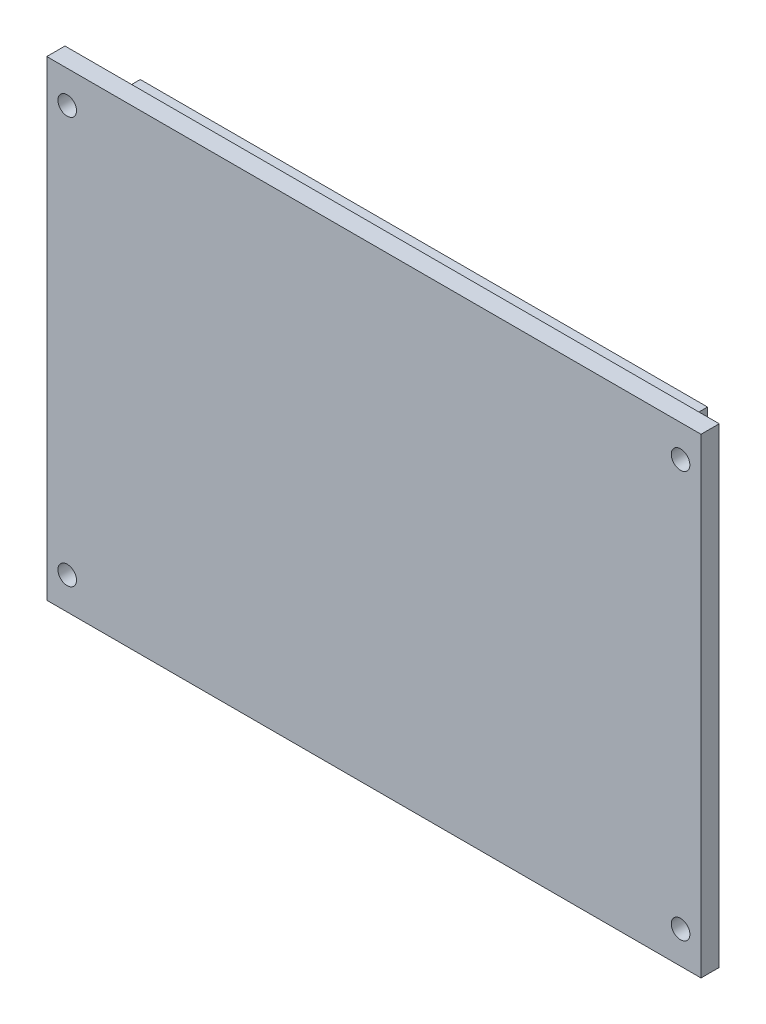
SolidWorks part; units mm, degrees
material "ABS"
ref_plane "Front Plane" through (0, 0, 0) normal (0, 0, 1) x (1, 0, 0)
ref_plane "Top Plane" through (0, 0, 0) normal (0, 1, 0) x (1, 0, 0)
ref_plane "Right Plane" through (0, 0, 0) normal (1, 0, 0) x (0, 0, -1)
sketch "Sketch1" plane through (0, 0, 0) normal (0, 1, 0) x (1, 0, 0)
  circle A0 centre (0, 0) radius 172.5
  dimension "D1" = 345
extrude "Boss-Extrude1" add sketch "Sketch1" along normal blind 10
sketch "Sketch2" plane through (0, 10, 0) normal (0, 1, 0) x (1, 0, 0)
  circle A0 centre (-75.91, -178.72) radius 48.41
  circle A1 centre (75.91, -178.72) radius 48.41
  dimension "D1" = 96.82
  dimension "D2" = 96.82
  dimension "D3" = 151.82
  dimension "D4" = 0
  dimension "D5" = 178.72
  dimension "D6" = 75.91
extrude "Cut-Extrude1" cut sketch "Sketch2" against normal blind 10
sketch "Sketch3" plane through (0, 10, 0) normal (0, 1, 0) x (1, 0, 0)
  line L0 (-75.91, -178.72) -> (75.91, -178.72)
  line L1 (-98.9683, -119.81) -> (98.9683, -119.81)
  line L2 (0, -178.72) -> (0, -205.4095)
  line L3 (0, -116.81) -> (0, -103.1109)
  line L4 (-97.8835, -116.81) -> (97.8835, -116.81)
  arc A0 (97.8835, -116.81) -> (-97.8835, -116.81) centre (0, 0) ccw
  arc A1 (98.9683, -119.81) -> (-98.9683, -119.81) centre (0, 0) ccw
  dimension "D1" = 304.8
  dimension "D2" = 3
  dimension "D4" = 0
extrude "Boss-Extrude2" add sketch "Sketch3" along normal blind 5 contours L1 A1 A0 L4 region at (0, 10, -154.9849)
sketch "Sketch4" plane through (0, 10, 0) normal (0, 1, 0) x (1, 0, 0)
  line L0 (-28.2612, -170.1692) -> (28.2612, -170.1692)
  line L1 (28.2612, -170.1692) -> (28.2612, -183.8361)
  line L2 (28.2612, -183.8361) -> (-30.3005, -183.8361)
  line L3 (-30.3005, -183.8361) -> (-28.2612, -170.1692)
extrude "Cut-Extrude2" cut sketch "Sketch4" against normal blind 497
sketch "Sketch5" plane through (0, 10, 0) normal (0, 1, 0) x (1, 0, 0)
  line L0 (-166.525, 159.566) -> (-166.525, -120.1627)
  line L1 (166.525, 178.4393) -> (166.525, -124.881)
  line L2 (-148.2899, 170.4208) -> (120.6541, 170.4208)
  line L3 (28.2612, -170.1692) -> (-28.2612, -170.1692) construction
  line L5 (-166.525, 170.4208) -> (166.525, 170.4208)
  line L6 (-166.525, 170.4208) -> (-166.525, -186.2191)
  line L7 (-166.525, -186.2191) -> (166.525, -186.2191)
  line L8 (166.525, 170.4208) -> (166.525, -186.2191)
  line L9 (-215.4787, 226.3504) -> (214.5081, 226.3504)
  line L10 (-215.4787, 226.3504) -> (-215.4787, -259.9327)
  line L11 (-215.4787, -259.9327) -> (214.5081, -259.9327)
  line L12 (214.5081, 226.3504) -> (214.5081, -259.9327)
  arc M6 (102.8405, -138.4922) -> (-102.8405, -138.4922) centre (0, 0) ccw
  dimension "D1" = 333.05
  dimension "D2" = 166.525
  dimension "D3" = 340.59
extrude "Cut-Extrude6" cut sketch "Sketch5" against normal blind 497 contours L2 M6 | L1 M6 | L0 M6 region at (-168.9186, 10, 0) region at (0, 10, -171.2529) region at (168.9186, 10, 0)
sketch "Sketch6" plane through (0, 10, 0) normal (0, 1, 0) x (1, 0, 0)
  line L0 (-97.8835, -116.81) -> (97.8835, -116.81)
  line L1 (-97.8835, -116.81) -> (-97.8835, -61.81)
  line L2 (97.8835, -116.81) -> (97.8835, -61.81)
  line L3 (97.8835, -61.81) -> (-97.8835, -61.81)
  line L4 (92.8835, -66.81) -> (-92.8835, -66.81)
  line L5 (-92.8835, -111.81) -> (-92.8835, -66.81)
  line L6 (-92.8835, -111.81) -> (92.8835, -111.81)
  line L7 (92.8835, -111.81) -> (92.8835, -66.81)
  dimension "D1" = 55
  dimension "D2" = 5
extrude "Boss-Extrude3" add sketch "Sketch6" along normal blind 133.35
sketch "Sketch7" plane through (0, 10, 0) normal (0, 1, 0) x (1, 0, 0)
  line L1 (-92.8835, -66.81) -> (92.8835, -66.81)
  line L2 (-92.8835, -66.81) -> (-92.8835, -111.81)
  line L3 (-92.8835, -111.81) -> (92.8835, -111.81)
  line L4 (92.8835, -66.81) -> (92.8835, -111.81)
extrude "Boss-Extrude4" add sketch "Sketch7" along normal blind 5
sketch "Sketch8" plane through (0, 10, 0) normal (0, 1, 0) x (1, 0, 0)
  line L0 (-112.8835, -61.81) -> (-112.8835, -101.2671)
  line L1 (-97.8835, -61.81) -> (97.8835, -61.81)
  line L2 (-97.8835, -61.81) -> (-97.8835, -115.8298)
  line L4 (97.8835, -61.81) -> (97.8835, -115.8298)
  line L6 (112.8835, -46.81) -> (112.8835, -101.2671)
  line L7 (-88.0285, -46.81) -> (112.8835, -46.81)
  line L8 (-112.8835, -46.81) -> (-112.8835, -131.81) construction
  line L9 (-112.8835, -131.81) -> (112.8835, -131.81) construction
  line L10 (112.8835, -46.81) -> (112.8835, -131.81) construction
  line L11 (74.9923, -131.81) -> (76.4976, -131.81)
  line L12 (-97.8835, -116.81) -> (97.8835, -116.81) construction
  line L13 (97.8835, -61.81) -> (97.8835, -116.81) construction
  line L14 (-97.8835, -61.81) -> (-97.8835, -116.81) construction
  line L15 (-112.8835, -46.81) -> (112.8835, -46.81) construction
  line L18 (-112.8835, -61.81) -> (-88.0285, -61.81)
  line L19 (-88.0285, -46.81) -> (-88.0285, -61.81)
  arc A1 (-112.8835, -101.2671) -> (-96.7117, -116.81) centre (0, 0) ccw
  arc A5 (97.8835, -115.8298) -> (112.8835, -101.2671) centre (0, 0) ccw
  line M3 (-97.8835, -116.81) -> (-97.8835, -61.81)
  line M5 (97.8835, -61.81) -> (97.8835, -116.81)
  dimension "D1" = 15
extrude "Boss-Extrude5" add sketch "Sketch8" along normal blind 8 contours L0 A1 L18 M3 | A5 L6 L7 L19 L1 M5 region at (-104.9975, 10, 85.5341) region at (29.9995, 10, 60.2371)
chamfer "Chamfer1" distance 8 angle 38 3 edges at (-97.8835, 18, 88.8199) (4.9275, 18, 61.81) (97.8835, 18, 88.8199) first distance on face at (-97.8835, 51.1, 100.8157) first distance on face at (-50.228, 47.3375, 61.81) first distance on face at (97.8835, 51.1, 100.8157)
fillet "Fillet1" radius 38 3 edges at (-97.8835, 26, 88.8199) (4.9275, 26, 61.81) (97.8835, 26, 88.8199)
sketch "Sketch9" plane through (0, 10, 0) normal (0, 1, 0) x (1, 0, 0)
  circle A0 centre (0, 0) radius 374.0793
extrude "Cut-Extrude7" cut sketch "Sketch9" against normal blind 93
sketch "Sketch10" plane through (0, 10, 0) normal (0, -1, 0) x (1, 0, 0)
  circle A0 centre (0, 0) radius 152.4
  circle A1 centre (0, 0) radius 229.3861
extrude "Cut-Extrude8" cut sketch "Sketch10" against normal blind 93 and the other way blind 93
sketch "Sketch11" plane through (0, 143.35, 0) normal (0, 1, 0) x (1, 0, 0)
  line L0 (47.0835, -61.81) -> (47.0835, -116.81)
  line L1 (97.8835, -61.81) -> (-97.8835, -61.81) construction
  line L2 (-97.8835, -116.81) -> (97.8835, -116.81) construction
  line L3 (97.8835, -116.81) -> (97.8835, -61.81) construction
  line L4 (47.0835, -61.81) -> (-97.8835, -61.81)
  line L5 (-97.8835, -61.81) -> (-97.8835, -116.81)
  line L6 (-97.8835, -116.81) -> (47.0835, -116.81)
  line L8 (-140.8808, -21.3721) -> (150.5625, -21.3721)
  line L9 (-140.8808, -21.3721) -> (-140.8808, -156.1708)
  line L10 (-140.8808, -156.1708) -> (150.5625, -156.1708)
  line L11 (150.5625, -21.3721) -> (150.5625, -156.1708)
  dimension "D1" = 50.8
extrude "Cut-Extrude9" cut sketch "Sketch11" against normal blind 143
sketch "Sketch12" plane through (0, 143.35, 0) normal (0, 1, 0) x (1, 0, 0)
  line L1 (47.0835, -61.81) -> (52.0835, -61.81)
  line L2 (47.0835, -61.81) -> (47.0835, -116.81)
  line L3 (47.0835, -116.81) -> (52.0835, -116.81)
  line L4 (52.0835, -61.81) -> (52.0835, -116.81)
  dimension "D1" = 5
extrude "Boss-Extrude6" add sketch "Sketch12" against normal up to surface (133.35 mm away) up to face at (-25.4, 10, 89.31)
sketch "Sketch13" plane through (-97.8835, 0, 0) normal (-1, 0, 0) x (0, 0, 1)
  line L0 (61.81, 10) -> (116.81, 10) construction
  circle A0 centre (89.4188, 75) radius 10
  dimension "D1" = 20
  dimension "D2" = 65
extrude "Cut-Extrude10" cut sketch "Sketch13" against normal blind 58
sketch "Sketch14" plane through (0, 143.35, 0) normal (0, 1, 0) x (1, 0, 0)
  line L1 (-92.8835, -66.81) -> (47.0835, -66.81)
  line L2 (-92.8835, -66.81) -> (-92.8835, -111.81)
  line L3 (-92.8835, -111.81) -> (47.0835, -111.81)
  line L4 (47.0835, -66.81) -> (47.0835, -111.81)
extrude "Boss-Extrude7" add sketch "Sketch14" against normal blind 5
sketch "Sketch15" plane through (0, 0, 116.81) normal (0, 0, 1) x (1, 0, 0)
  line L1 (-92.8835, 138.35) -> (47.0835, 138.35)
  line L2 (-92.8835, 138.35) -> (-92.8835, 15)
  line L3 (-92.8835, 15) -> (47.0835, 15)
  line L4 (47.0835, 138.35) -> (47.0835, 15)
extrude "Cut-Extrude11" cut sketch "Sketch15" against normal blind 13
sketch "Sketch16" plane through (0, 0, 116.81) normal (0, 0, 1) x (1, 0, 0)
  line L0 (-107.8835, 143.35) -> (-107.8835, 10)
  line L1 (-92.8835, 138.35) -> (47.0835, 138.35)
  line L2 (-92.8835, 138.35) -> (-92.8835, 15)
  line L3 (-92.8835, 15) -> (47.0835, 15)
  line L4 (47.0835, 138.35) -> (47.0835, 15)
  line L6 (62.0835, 143.35) -> (62.0835, 10)
  line L8 (-107.8835, 143.35) -> (62.0835, 143.35)
  line L9 (-107.8835, 10) -> (62.0835, 10)
  line L10 (-107.8835, 153.35) -> (-107.8835, 0) construction
  line L11 (-107.8835, 0) -> (62.0835, 0) construction
  line L12 (62.0835, 153.35) -> (62.0835, 0) construction
  line L13 (-107.8835, 153.35) -> (62.0835, 153.35) construction
  line L14 (-92.8835, 76.675) -> (47.0835, 76.675)
  line L15 (-92.8835, 127.475) -> (47.0835, 127.475)
  line L16 (-92.8835, 127.475) -> (-92.8835, 25.875)
  line L17 (-92.8835, 25.875) -> (47.0835, 25.875)
  line L18 (47.0835, 127.475) -> (47.0835, 25.875)
  line L19 (-22.9, 127.475) -> (-22.9, 25.875)
  point P22 (-92.8835, 76.675)
  point P25 (-22.9, 138.35)
  line M11 (47.0835, 15) -> (-92.8835, 15)
  line M12 (-92.8835, 15) -> (-92.8835, 138.35)
  line M13 (-92.8835, 138.35) -> (47.0835, 138.35)
  line M14 (47.0835, 138.35) -> (47.0835, 15)
  line M15 (-97.8835, 10) -> (52.0835, 10)
  line M16 (52.0835, 10) -> (52.0835, 143.35)
  line M17 (52.0835, 143.35) -> (-97.8835, 143.35)
  line M18 (-97.8835, 143.35) -> (-97.8835, 10)
  dimension "D2" = 101.6
  dimension "D3" = 0
  dimension "D4" = 0
  dimension "D5" = 0
  dimension "D1" = 15
extrude "Boss-Extrude9" add sketch "Sketch16" against normal blind 17 contours L0 L9 L8 M18 | L4 L2 M18 M15 M16 M17 M14 M11 M12 M13 | L9 L6 L8 M16 | L15 M12 M14 M13 | L17 M12 M11 M14 region at (-102.8835, 76.675, 116.81) region at (-22.9, 141.3432, 116.81) region at (57.0835, 76.675, 116.81) region at (-22.9, 132.9125, 116.81) region at (-22.9, 20.4375, 116.81)
sketch "Sketch17" plane through (0, 0, 116.81) normal (0, 0, 1) x (1, 0, 0)
  line L0 (-95.8835, 130.475) -> (-95.8835, 22.875)
  line L1 (-92.8835, 127.475) -> (47.0835, 127.475)
  line L2 (-92.8835, 127.475) -> (-92.8835, 25.875)
  line L3 (-92.8835, 25.875) -> (47.0835, 25.875)
  line L4 (47.0835, 127.475) -> (47.0835, 25.875)
  line L5 (-95.8835, 22.875) -> (50.0835, 22.875)
  line L6 (50.0835, 130.475) -> (50.0835, 22.875)
  line L7 (-95.8835, 130.475) -> (50.0835, 130.475)
  line L8 (-99.8835, 134.475) -> (54.0835, 134.475)
  line L9 (54.0835, 134.475) -> (54.0835, 18.875)
  line L10 (-99.8835, 18.875) -> (54.0835, 18.875)
  line L11 (-99.8835, 134.475) -> (-99.8835, 18.875)
  dimension "D1" = 3
  dimension "D2" = 4
extrude "Cut-Extrude12" cut sketch "Sketch17" against normal blind 10 contours L8 L11 L10 L9 L0 L7 L6 L5 region at (-22.9, 132.5497, 116.81)
sketch "Sketch20" plane through (0, 0, 116.81) normal (0, 0, 1) x (1, 0, 0)
  line L0 (-107.8835, 143.35) -> (-107.8835, 10) construction
  line L1 (-110.8835, 146.35) -> (65.0835, 146.35)
  line L2 (-110.8835, 146.35) -> (-110.8835, 7)
  line L3 (-110.8835, 7) -> (65.0835, 7)
  line L4 (65.0835, 146.35) -> (65.0835, 7)
  line L5 (62.0835, 143.35) -> (62.0835, 10) construction
  line L6 (-107.8835, 10) -> (62.0835, 10) construction
  line L7 (-107.8835, 143.35) -> (62.0835, 143.35) construction
  line L9 (-107.8835, 143.35) -> (62.0835, 143.35)
  line L10 (-107.8835, 143.35) -> (-107.8835, 10)
  line L11 (-107.8835, 10) -> (62.0835, 10)
  line L12 (62.0835, 143.35) -> (62.0835, 10)
  line L13 (-110.8835, 7) -> (65.0835, 7)
  line L14 (-110.8835, 7) -> (-110.8835, 13.35)
  line L15 (-110.8835, 13.35) -> (65.0835, 13.35)
  line L16 (65.0835, 7) -> (65.0835, 13.35)
  line M13 (-107.8835, 10) -> (62.0835, 10)
  line M14 (62.0835, 10) -> (62.0835, 143.35)
  dimension "D1" = 3
  dimension "D2" = 3
  dimension "D3" = 3
  dimension "D4" = 3
  dimension "D5" = 6.35
chamfer "Chamfer2" distance 10 angle 30 2 edges at (-22.9, 25.875, 99.81) (-22.9, 127.475, 99.81) first distance on face at (-22.9, 25.875, 108.31) first distance on face at (-22.9, 132.9125, 99.81)
sketch "Sketch24" plane through (-97.8835, 0, 0) normal (-1, 0, 0) x (0, 0, 1)
  line L0 (99.81, 143.35) -> (99.81, 10) construction
  circle A1 centre (83.81, 75) radius 15
  dimension "D1" = 30
  dimension "D2" = 16
extrude "Cut-Extrude16" cut sketch "Sketch24" against normal blind 177.5
extrude "Cut-Extrude17" cut sketch "Sketch20" against normal blind 177.5 contours L15 L2 L3 L4 L10 M14 M13 | L15 L10 M13 M14 region at (-22.9, 8.6165, 116.81) region at (-22.9, 11.675, 116.81)
sketch "Sketch25" plane through (0, 13.35, 0) normal (0, -1, 0) x (-1, 0, 0)
  line L1 (-47.0835, -66.81) -> (92.8835, -66.81)
  line L2 (-47.0835, -66.81) -> (-47.0835, -105.5835)
  line L3 (-47.0835, -105.5835) -> (92.8835, -105.5835)
  line L4 (92.8835, -66.81) -> (92.8835, -105.5835)
extrude "Boss-Extrude11" add sketch "Sketch25" against normal blind 5
sketch "Sketch26" plane through (0, 0, 116.81) normal (0, 0, 1) x (1, 0, 0)
  line L0 (-107.8835, 143.35) -> (-107.8835, 13.35) construction
  line L1 (-110.8835, 143.35) -> (-107.8835, 143.35)
  line L2 (-110.8835, 143.35) -> (-110.8835, 13.35)
  line L3 (-110.8835, 13.35) -> (-107.8835, 13.35)
  line L4 (65.0835, 143.35) -> (65.0835, 13.35)
  line L5 (62.0835, 143.35) -> (62.0835, 13.35) construction
  line L6 (62.0835, 13.35) -> (65.0835, 13.35)
  line L8 (-107.8835, 143.35) -> (-107.8835, 13.35)
  line L10 (62.0835, 143.35) -> (62.0835, 13.35)
  line L11 (62.0835, 143.35) -> (65.0835, 143.35)
  dimension "D1" = 3
  dimension "D2" = 3
extrude "Boss-Extrude12" add sketch "Sketch26" against normal up to surface (17 mm away) up to face at (57.0835, 78.35, 99.81)
sketch "Sketch18" plane through (0, 0, 116.81) normal (0, 0, 1) x (1, 0, 0)
  line L7 (-99.8835, 134.475) -> (-99.8835, 18.875) construction
  line L8 (54.0835, 134.475) -> (54.0835, 18.875) construction
  circle A2 centre (-105.3835, 22) radius 2.5
  circle A3 centre (59.5835, 22) radius 2.5
  circle A4 centre (59.5835, 131.35) radius 2.5
  circle A5 centre (-105.3835, 131.35) radius 2.5
  point P10 (-22.9, 76.675)
  dimension "D4" = 5
  dimension "D5" = 5
  dimension "D10" = 5.5
  dimension "D12" = 5.5
extrude "Cut-Extrude19" cut sketch "Sketch18" against normal blind 26
sketch "Sketch27" plane through (0, 0, 116.81) normal (0, 0, 1) x (1, 0, 0)
  line L0 (-99.1835, 133.775) -> (-99.1835, 19.575)
  line L1 (-99.8835, 134.475) -> (54.0835, 134.475)
  line L2 (-99.8835, 134.475) -> (-99.8835, 18.875)
  line L3 (-99.8835, 18.875) -> (54.0835, 18.875)
  line L4 (54.0835, 134.475) -> (54.0835, 18.875)
  line L5 (-99.1835, 19.575) -> (53.3835, 19.575)
  line L6 (53.3835, 133.775) -> (53.3835, 19.575)
  line L7 (-99.1835, 133.775) -> (53.3835, 133.775)
  line L8 (46.3835, 26.575) -> (46.3835, 126.775)
  line L9 (-95.8835, 130.475) -> (50.0835, 130.475)
  line L10 (-95.8835, 130.475) -> (-95.8835, 22.875)
  line L11 (-95.8835, 22.875) -> (50.0835, 22.875)
  line L12 (50.0835, 130.475) -> (50.0835, 22.875)
  line L13 (47.0835, 25.875) -> (-92.8835, 25.875)
  line L14 (47.0835, 25.875) -> (47.0835, 127.475)
  line L15 (47.0835, 127.475) -> (-92.8835, 127.475)
  line L16 (-92.8835, 25.875) -> (-92.8835, 127.475)
  line L17 (46.3835, 126.775) -> (-92.1835, 126.775)
  line L18 (-92.1835, 26.575) -> (-92.1835, 126.775)
  line L19 (46.3835, 26.575) -> (-92.1835, 26.575)
  line L20 (-96.5835, 131.175) -> (50.7835, 131.175)
  line L21 (50.7835, 131.175) -> (50.7835, 22.175)
  line L22 (-96.5835, 22.175) -> (50.7835, 22.175)
  line L23 (-96.5835, 131.175) -> (-96.5835, 22.175)
  dimension "D1" = 0.7
  dimension "D2" = 0.7
  dimension "D3" = 0.7
extrude "Boss-Extrude13" add sketch "Sketch27" against normal blind 8.45 separate body contours L7 L0 L5 L6 L23 L20 L21 L22 | L19 L8 L17 L18 region at (-22.9, 131.8693, 116.81) region at (-22.9, 76.675, 116.81)
sketch "Sketch28" plane through (0, 0, 116.81) normal (0, 0, 1) x (1, 0, 0)
  line L1 (-110.8835, 143.35) -> (65.0835, 143.35)
  line L2 (-110.8835, 143.35) -> (-110.8835, 13.35)
  line L3 (-110.8835, 13.35) -> (65.0835, 13.35)
  line L4 (65.0835, 143.35) -> (65.0835, 13.35)
  circle A0 centre (-105.3835, 131.35) radius 2.5
  circle A1 centre (59.5835, 131.35) radius 2.5
  circle A2 centre (59.5835, 22) radius 2.5
  circle A3 centre (-105.3835, 22) radius 2.5
extrude "Boss-Extrude14" add sketch "Sketch28" along normal blind 5
sketch "Sketch29" plane through (0, 0, 61.81) normal (0, 0, -1) x (-1, 0, 0)
  line L1 (-138.5926, 160.545) -> (153.936, 160.545)
  line L2 (-138.5926, 160.545) -> (-138.5926, -10.7704)
  line L3 (-138.5926, -10.7704) -> (153.936, -10.7704)
  line L4 (153.936, 160.545) -> (153.936, -10.7704)
extrude "Cut-Extrude20" cut sketch "Sketch29" against normal up to surface (46.55 mm away) up to face at (-22.9, 76.675, 108.36)
sketch "Sketch30" plane through (0, 0, 108.36) normal (0, 0, -1) x (-1, 0, 0)
  line L1 (-65.0835, 143.35) -> (110.8835, 143.35)
  line L2 (-65.0835, 143.35) -> (-65.0835, 13.35)
  line L3 (-65.0835, 13.35) -> (110.8835, 13.35)
  line L4 (110.8835, 143.35) -> (110.8835, 13.35)
  line L5 (-46.3835, 126.775) -> (92.1835, 126.775)
  line L6 (-46.3835, 126.775) -> (-46.3835, 26.575)
  line L7 (-46.3835, 26.575) -> (92.1835, 26.575)
  line L8 (92.1835, 126.775) -> (92.1835, 26.575)
  line L9 (95.8835, 22.875) -> (-50.0835, 22.875)
  line L10 (95.8835, 22.875) -> (95.8835, 130.475)
  line L11 (95.8835, 130.475) -> (-50.0835, 130.475)
  line L12 (-50.0835, 22.875) -> (-50.0835, 130.475)
  line L13 (-54.0835, 134.475) -> (99.8835, 134.475)
  line L14 (-54.0835, 134.475) -> (-54.0835, 18.875)
  line L15 (-54.0835, 18.875) -> (99.8835, 18.875)
  line L16 (99.8835, 134.475) -> (99.8835, 18.875)
  line M1 (-46.3835, 26.575) -> (92.1835, 26.575)
  line M2 (92.1835, 26.575) -> (92.1835, 126.775)
  line M3 (92.1835, 126.775) -> (-46.3835, 126.775)
  line M4 (-46.3835, 126.775) -> (-46.3835, 26.575)
extrude "Cut-Extrude23" cut sketch "Sketch30" against normal offset from surface (8.55 mm away) 4.9 contours L12 L9 L10 L11 M1 M4 M3 M2 | L4 L1 L2 L3 L13 L16 L15 L14 region at (-22.9, 141.1622, 108.36) region at (-22.9, 24.6884, 108.36) up to face at (62.0835, 22, 121.81)
sketch "Sketch31" plane through (0, 0, 116.91) normal (0, 0, -1) x (-1, 0, 0)
  line L0 (-65.0835, 13.35) -> (110.8835, 13.35)
  line L1 (110.8835, 13.35) -> (110.8835, -3.8462)
  line L2 (110.8835, -3.8462) -> (-65.0835, -3.8462)
  line L3 (-65.0835, -3.8462) -> (-65.0835, 13.35)
  line L4 (-46.3835, 76.675) -> (-23.0864, 76.675) construction
  line L5 (-46.3835, 26.575) -> (-46.3835, 126.775) construction
  line L6 (-65.0835, 157.1962) -> (-65.0835, 140)
  line L7 (110.8835, 157.1962) -> (-65.0835, 157.1962)
  line L8 (110.8835, 140) -> (110.8835, 157.1962)
  line L9 (-65.0835, 140) -> (110.8835, 140)
  line L10 (-65.0835, 143.35) -> (110.8835, 143.35) construction
  dimension "D1" = 3.35
extrude "Cut-Extrude24" cut sketch "Sketch31" against normal blind 10
